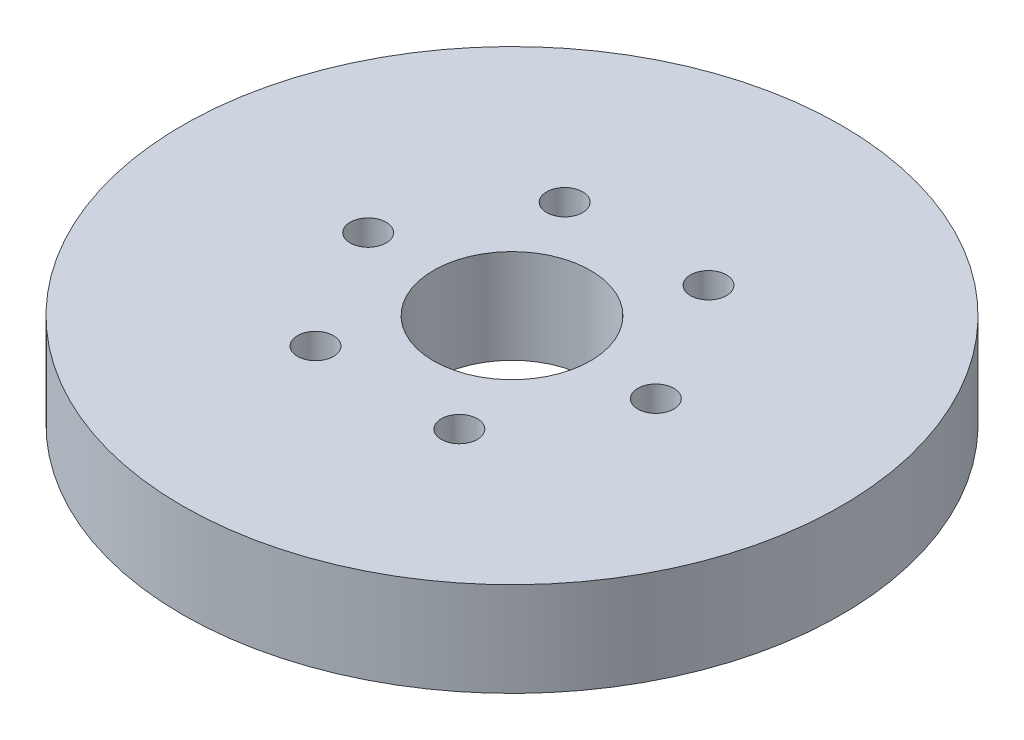
SolidWorks part; units mm, degrees
ref_plane "Front Plane" through (0, 0, 0) normal (0, 0, 1) x (1, 0, 0)
ref_plane "Top Plane" through (0, 0, 0) normal (0, 1, 0) x (1, 0, 0)
ref_plane "Right Plane" through (0, 0, 0) normal (1, 0, 0) x (0, 0, -1)
sketch "Sketch1" plane through (0, 0, 0) normal (0, 1, 0) x (1, 0, 0)
  circle A0 centre (0, 0) radius 52.5
  dimension "FLANGE_OD" = 105
extrude "Boss-Extrude1" add sketch "Sketch1" along normal blind 15
sketch "Sketch2" plane through (0, 0, 0) normal (0, 1, 0) x (1, 0, 0)
  circle A0 centre (0, 0) radius 12.5
  dimension "BORE_D" = 25
extrude "Cut-Extrude1" cut sketch "Sketch2" along normal through all
sketch "Sketch3" plane through (0, 15, 0) normal (0, 1, 0) x (1, 0, 0)
  circle A0 centre (0, 0) radius 22.9135 construction
  circle A1 centre (-22.9135, 0) radius 2.8689
  dimension "BOLT_D" = 5.7378
  dimension "BOLT_PCD" = 45.8269
extrude "Cut-Extrude2" cut sketch "Sketch3" against normal blind 14.0035
pattern_circular "CirPattern1" count 6 over 360 about axis through (0, 0, 0) along (0, 1, 0) of "Cut-Extrude2"
